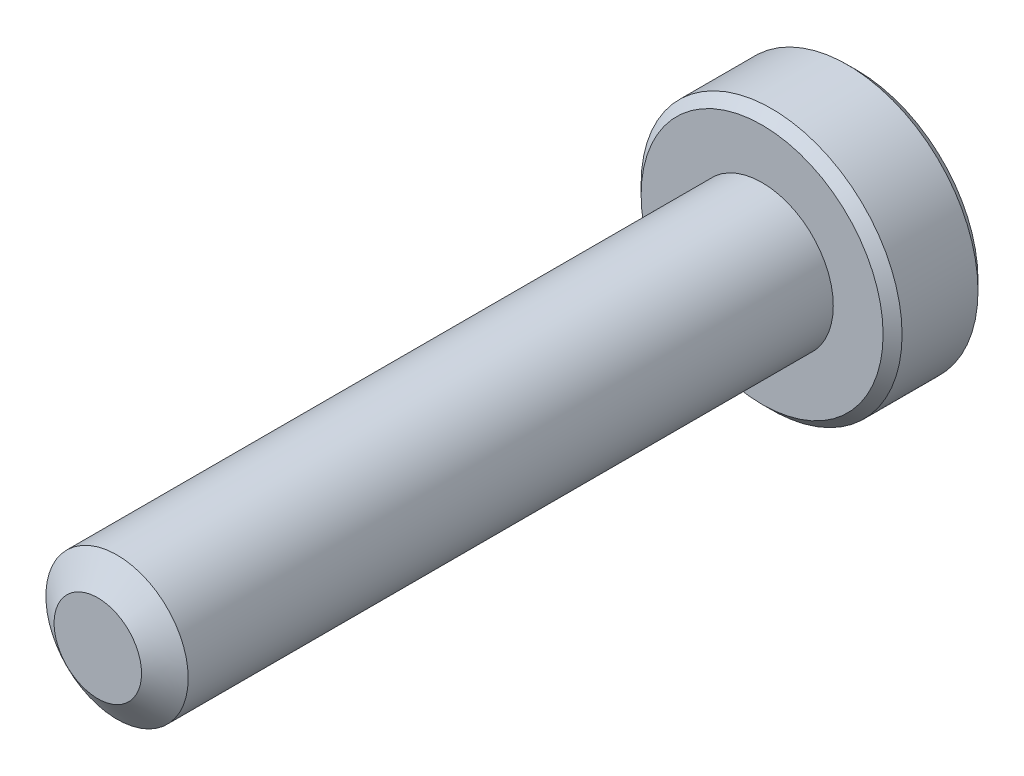
SolidWorks part; units mm, degrees
ref_plane "Front Plane" through (0, 0, 0) normal (0, 0, 1) x (1, 0, 0)
ref_plane "Top Plane" through (0, 0, 0) normal (0, 1, 0) x (1, 0, 0)
ref_plane "Right Plane" through (0, 0, 0) normal (1, 0, 0) x (0, 0, -1)
sketch "Sketch1" plane through (0, 0, 0) normal (0, 0, 1) x (1, 0, 0)
  circle A0 centre (0, 0) radius 1.5
  dimension "OD" = 3
extrude "Extrude1" add sketch "Sketch1" against normal blind 14
sketch "Sketch2" plane through (0, 0, 0) normal (0, 0, 1) x (1, 0, 0)
  circle A0 centre (0, 0) radius 1.5 construction
  circle A1 centre (0, 0) radius 1.5
curve "Helix/Spiral1" pitch 0.5 height 14.5 turns 29 parameters "pitch"=0.5
sketch "Sketch3" plane through (0, 0, 0) normal (1, 0, 0) x (0, 0, -1)
  line L0 (-0.4375, 1.5) -> (-0.25, 1.1752)
  line L1 (-0.25, 1.1752) -> (-0.1875, 1.1752)
  line L2 (-0.1875, 1.1752) -> (0, 1.5)
  line L3 (-0.4375, 1.5) -> (0, 1.5)
  line L4 (-0.2187, 1.5) -> (-0.2187, 1.1752) construction
  line L5 (-0.3437, 1.3376) -> (-0.0937, 1.3376) construction
  line L6 (0, 1.5) -> (0, -1.5) construction
  dimension "D1" = 0.0625
  dimension "D2" = 0.25
  dimension "D3" = 60
sweep "Cut-Sweep1" [suppressed] cut profiles "Sketch3" path "Helix/Spiral1"
sketch "Sketch4" plane through (0, 0, 0) normal (1, 0, 0) x (0, 0, -1)
  line L0 (0.4053, 1.5) -> (0, 0.9212)
  line L1 (0, 0.9212) -> (0, 1.5)
  line L2 (0.4053, 1.5) -> (0, 1.5)
  line L3 (-0.4375, 1.5) -> (0, 1.5) construction
  line L4 (0, 0) -> (7.0209, 0) construction
  dimension "D1" = 55
  dimension "D2" = 0.254
revolve "Cut-Revolve1" cut sketch "Sketch4" angle 360 about L4
sketch "Sketch6" plane through (0, 0, -14) normal (0, 0, -1) x (-1, 0, 0)
  circle A0 centre (0, 0) radius 2.75
  dimension "head dia" = 5.5
extrude "Extrude2" add sketch "Sketch6" along normal blind 2
sketch "Sketch5" plane through (0, 0, 0) normal (1, 0, 0) x (0, 0, -1)
  line L1 (14, 1.5) -> (18.1202, 1.5)
  line L2 (14, 1.5) -> (14, 0)
  line L3 (14, 0) -> (18, 0)
  line L4 (18, 1.1698) -> (18, 0)
  line L5 (18.1202, 1.5) -> (18, 1.1698)
  line L6 (0, 0) -> (9.9695, 0) construction
  line L7 (14, 2.75) -> (14, -2.75) construction
  point P3 (18, 1.5)
  point P10 (18, 1.5)
  dimension "D1" = 0.3302
  dimension "Thread min" = 18
  dimension "D2" = 1.5
  dimension "D3" = 20
revolve "partially thread" [suppressed] add sketch "Sketch5" angle 360 about L6
sketch "Sketch7" plane through (0, 0, -16) normal (0, 0, -1) x (-1, 0, 0)
  line L1 (0, 1.1547) -> (-1, 0.5774)
  line L2 (-1, 0.5774) -> (-1, -0.5774)
  line L3 (-1, -0.5774) -> (0, -1.1547)
  line L4 (0, -1.1547) -> (1, -0.5774)
  line L5 (1, -0.5774) -> (1, 0.5774)
  line L6 (1, 0.5774) -> (0, 1.1547)
  circle A0 centre (0, 0) radius 1 construction
  dimension "hex dia" = 2
extrude "Cut-Extrude1" cut sketch "Sketch7" against normal blind 1.5
sketch "Sketch8" plane through (0, 0, -16) normal (0, 0, -1) x (-1, 0, 0)
  circle A0 centre (0, 0) radius 1.1547
extrude "Cut-Extrude2" cut sketch "Sketch8" against normal through all draft 45
chamfer "Chamfer1" distance 0.2 angle 45 2 edges at (-2.75, 0, -16) (-2.75, 0, -14)
sketch "Sketch9" plane through (0, 0, 0) normal (1, 0, 0) x (0, 0, -1)
  line L0 (0, 1.5) -> (0, -1.5) construction
  line L1 (2.75, 1.5) -> (2.75, -1.5) construction
  dimension "D1" = 2.75
equation "\"D3@Helix/Spiral1\" = \"screw length@Extrude1\"+\"pitch@Helix/Spiral1\""
equation "\"D1@Sketch3\" = \"pitch@Helix/Spiral1\"*.125"
equation "\"D2@Sketch3\" = \"pitch@Helix/Spiral1\"*.5"
equation "\"D1@Cut-Extrude1\" = \"hex dia@Sketch7\"*.75"
equation "\"D1@Chamfer1\" = \"head depth@Extrude2\"*.1"
equation "\"D1@Sketch9\" = \"pitch@Helix/Spiral1\"*5.5"
equation "\"D2@Sketch5\" = \"OD@Sketch1\"/2"
